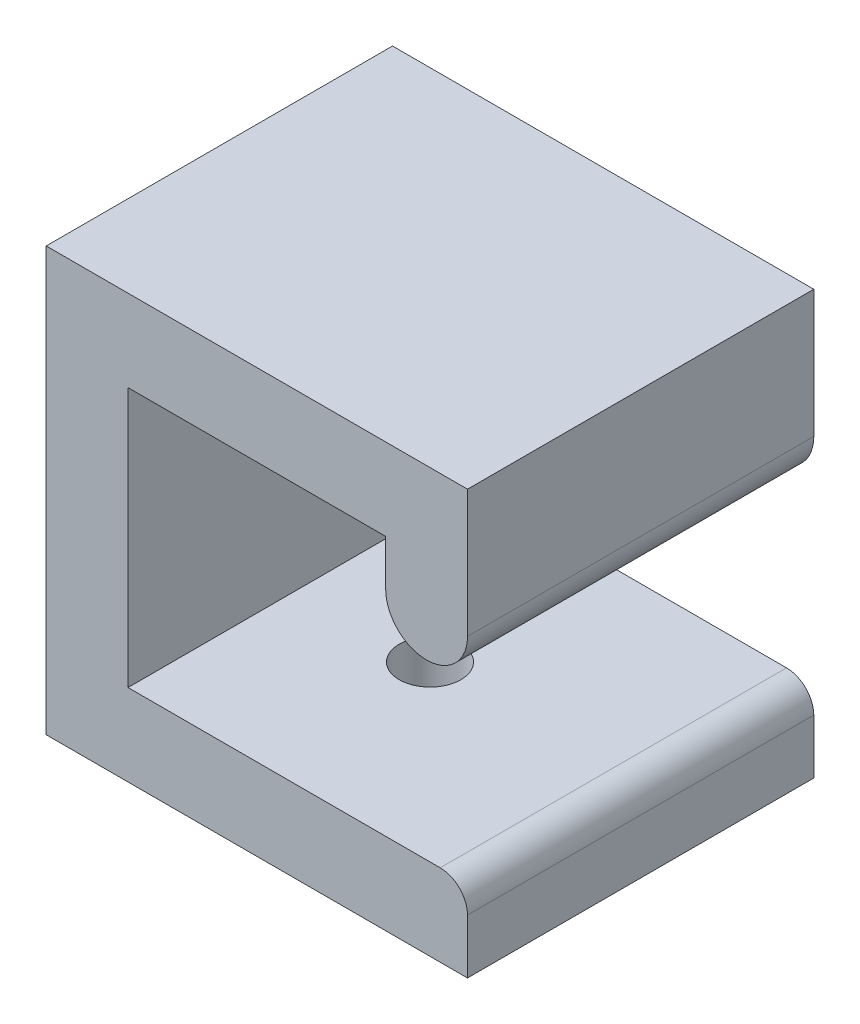
SolidWorks part; units mm, degrees
ref_plane "Front Plane" through (0, 0, 0) normal (0, 0, 1) x (1, 0, 0)
ref_plane "Top Plane" through (0, 0, 0) normal (0, 1, 0) x (1, 0, 0)
ref_plane "Right Plane" through (0, 0, 0) normal (1, 0, 0) x (0, 0, -1)
sketch "Sketch1" plane through (0, 0, 0) normal (0, 0, 1) x (1, 0, 0)
  line L2 (-146.8124, 5.1981) -> (-162.2624, 5.1981)
  line L3 (-162.2624, 5.1981) -> (-162.2624, -10.3269)
  line L4 (-162.2624, -10.3269) -> (-146.8124, -10.3269)
  line L5 (-146.8124, -10.3269) -> (-146.8124, -7.3269)
  line L6 (-146.8124, -7.3269) -> (-159.2624, -7.3269)
  line L7 (-159.2624, -7.3269) -> (-159.2624, 2.1981)
  line L9 (-159.2624, 2.1981) -> (-149.8124, 2.1981)
  line L12 (-159.2624, 2.1981) -> (-159.2624, -0.9769) construction
  line L13 (43.9376, 2.1981) -> (31.2376, 2.1981) construction
  line L14 (-146.8124, 5.1981) -> (-146.8124, 2.1981)
  line L15 (43.9376, 2.1981) -> (31.2376, 2.1981) construction
  line L18 (-149.8124, 2.1981) -> (-149.8124, 0.5231)
  line L19 (-146.8124, 2.1981) -> (-146.8124, 0.5231)
  line L20 (43.9376, -0.9769) -> (31.2376, -0.9769) construction
  line L21 (-141.4824, -7.3269) -> (26.1576, -7.3269) construction
  line L22 (26.1576, 2.1981) -> (-141.4824, 2.1981) construction
  line L24 (-149.8124, 2.1981) -> (-149.8124, -0.9769) construction
  arc A4 (-149.8124, 0.5231) -> (-146.8124, 0.5231) centre (-148.3124, 0.5231) ccw
  dimension "D4" = 3
  dimension "D1" = 3
  dimension "D2" = 3
  dimension "D3" = 3
extrude "MainBody" add sketch "Sketch1" along normal blind 12.7
hole_wizard "#4-40 Tapped Hole1" positions "Sketch3" profile "Sketch4" tap size "#4-40" standard "ANSI Inch" end condition up to next
sketch "Sketch3" plane through (0, -10.3269, 0) normal (0, -1, 0) x (-1, 0, 0)
  line L0 (162.2624, -12.7) -> (146.8124, -12.7) construction
  line L1 (146.8124, -12.7) -> (146.8124, 0) construction
  point P2 (154.5374, -6.35)
  point P6 (154.5374, -12.7)
  point P9 (146.8124, -6.35)
sketch "Sketch4" plane through (-154.5374, -10.3269, 6.35) normal (1, 0, 0) x (0, 0, -1)
  line L0 (0, 0) -> (0, 3)
  line L1 (0, 3) -> (1.1303, 3)
  line L2 (1.1303, 3) -> (1.1303, 0)
  line L5 (1.1303, 0) -> (0, 0)
  line L11 (0, -6.35) -> (0, 107.95) construction
  dimension "Thru Tap Drill Dia." = 2.2606
  dimension "Thru Tap Drill Depth" = 3
cosmetic thread "Hole Thread3"
fillet "Fillet4" radius 1 1 edges at (-146.8124, -7.3269, 6.35)
